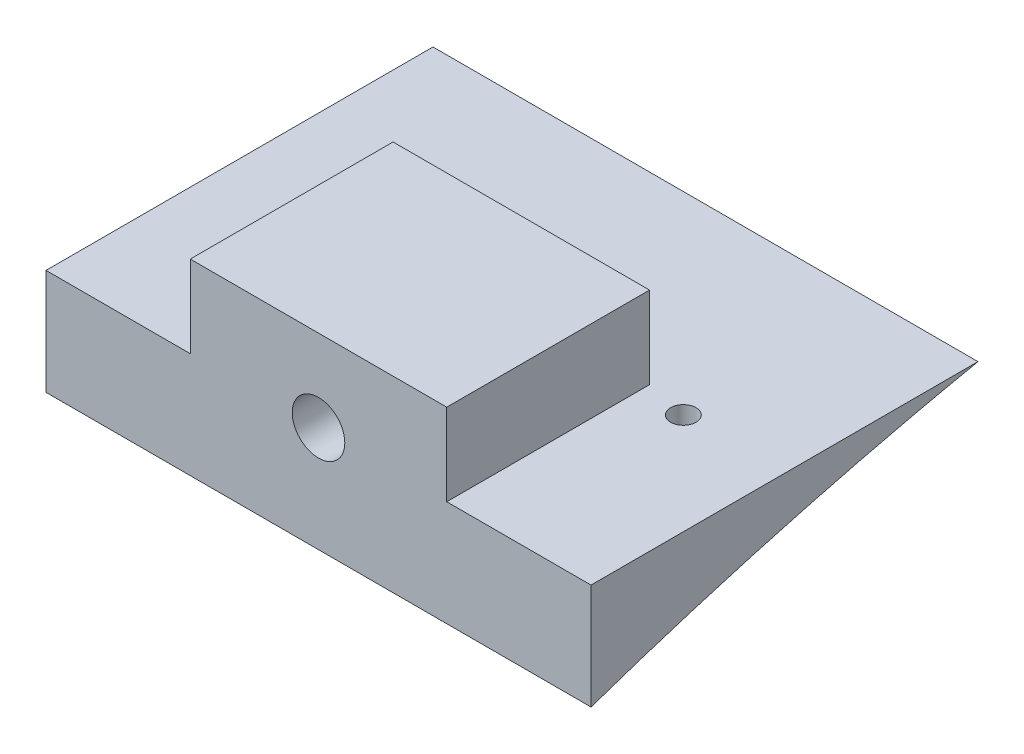
SolidWorks part; units mm, degrees
material "ABS"
ref_plane "Front Plane" through (0, 0, 0) normal (0, 0, 1) x (1, 0, 0)
ref_plane "Top Plane" through (0, 0, 0) normal (0, 1, 0) x (1, 0, 0)
ref_plane "Right Plane" through (0, 0, 0) normal (1, 0, 0) x (0, 0, -1)
curve "Curve1"
  spline degree 3 poles (0, 0.0012, 1.0003) (0, 0.0015, 0.9994) (0, 0.0028, 0.9958) (0, 0.0055, 0.9879) (0, 0.0099, 0.9747) (0, 0.0159, 0.9565) (0, 0.0233, 0.9333) (0, 0.0318, 0.9054) (0, 0.0411, 0.8731) (0, 0.051, 0.8366) (0, 0.0612, 0.7964) (0, 0.0713, 0.7528) (0, 0.0811, 0.7063) (0, 0.0903, 0.6574) (0, 0.0985, 0.6067) (0, 0.1057, 0.5546) (0, 0.1115, 0.5018) (0, 0.1158, 0.4488) (0, 0.1186, 0.3959) (0, 0.1189, 0.3436) (0, 0.1164, 0.2927) (0, 0.1112, 0.2442) (0, 0.1037, 0.1988) (0, 0.0942, 0.157) (0, 0.0831, 0.1194) (0, 0.0711, 0.0865) (0, 0.0584, 0.0585) (0, 0.0457, 0.0357) (0, 0.0334, 0.0184) (0, 0.0218, 0.0064) (0, 0.0108, -0.0005) (0, -0.0003, -0.0011) (0, -0.0092, 0.0055) (0, -0.0148, 0.017) (0, -0.0185, 0.0329) (0, -0.0204, 0.0533) (0, -0.0208, 0.0781) (0, -0.0198, 0.107) (0, -0.0176, 0.1398) (0, -0.0147, 0.176) (0, -0.0111, 0.2153) (0, -0.0074, 0.2574) (0, -0.0037, 0.3019) (0, -0.0005, 0.3484) (0, 0.002, 0.397) (0, 0.0037, 0.4471) (0, 0.0055, 0.4983) (0, 0.0069, 0.5496) (0, 0.0079, 0.6006) (0, 0.0085, 0.6505) (0, 0.0086, 0.699) (0, 0.0083, 0.7455) (0, 0.0076, 0.7894) (0, 0.0065, 0.8302) (0, 0.0053, 0.8675) (0, 0.0039, 0.9007) (0, 0.0027, 0.9296) (0, 0.0013, 0.9539) (0, 0.0006, 0.9727) (0, -0.0011, 0.9872) (0, 0, 0.9944) (0, -0.002, 0.9999) (0, -0.0005, 1) (0, 0, 1) knots 0 0 0 0 0.001372 0.005465 0.012235 0.021602 0.033461 0.047671 0.064081 0.082496 0.102719 0.124527 0.147676 0.171913 0.196978 0.222597 0.248497 0.274385 0.300041 0.32569 0.350525 0.37428 0.396711 0.417577 0.436654 0.453744 0.46868 0.481329 0.491631 0.499616 0.505546 0.510185 0.514824 0.520702 0.528516 0.538466 0.550543 0.564643 0.580638 0.598345 0.617584 0.638174 0.659922 0.682632 0.706121 0.730727 0.7557 0.780732 0.805564 0.829932 0.85357 0.876213 0.89761 0.917519 0.935698 0.951943 0.966047 0.97784 0.987174 0.993932 0.998018 0.999386 1 1 1 1
sketch "Sketch1" plane through (0, 0, 0) normal (1, 0, 0) x (0, 0, -1)
  line L3 (195.725, 0) -> (-195.725, 0) construction
  line L4 (-258.7498, 26.4626) -> (-355.6872, 26.4626)
  line L5 (-355.6872, 26.4626) -> (-355.6872, 0)
  spline S1 degree 3 poles (-355.6872, 0) (-355.3706, 0.108) (-354.109, 0.5382) (-351.285, 1.5029) (-346.6023, 3.0589) (-336.8154, 6.2519) (-320.4299, 11.2778) (-301.3571, 16.5496) (-283.1673, 21.0862) (-270.1079, 24.0716) (-261.8289, 25.8283) (-258.7498, 26.4626) knots 0 0 0 0 0.001372 0.005465 0.012235 0.021602 0.047671 0.082496 0.102719 0.124527 0.137416 0.137416 0.137416 0.137416
  dimension "D1" = 26.4626
  dimension "D2" = 355.6872
  dimension "D3" = 96.9374
extrude "Boss-Extrude1" add sketch "Sketch1" along normal mid plane 136.525
sketch "Sketch2" plane through (0, 26.4626, 0) normal (0, 1, 0) x (1, 0, 0)
  line L0 (-68.2625, -307.2185) -> (68.2625, -307.2185) construction
  line L1 (-68.2625, -258.7498) -> (-68.2625, -355.6872) construction
  line L2 (68.2625, -258.7498) -> (68.2625, -355.6872) construction
  line L3 (-42.926, -307.2185) -> (-42.926, -258.7498) construction
  line L4 (68.2625, -258.7498) -> (-68.2625, -258.7498) construction
  line L5 (42.926, -307.2185) -> (42.926, -258.7498) construction
  line L6 (-68.2625, -286.8403) -> (-42.926, -286.8403) construction
  line L7 (-42.926, -286.8403) -> (42.926, -286.8403) construction
  line L8 (42.926, -286.8403) -> (68.2625, -286.8403) construction
  circle A0 centre (-42.926, -307.2185) radius 3.175
  circle A1 centre (42.926, -307.2185) radius 3.175
  dimension "D1" = 6.35
  dimension "D2" = 6.35
  dimension "D3" = 85.852
extrude "Cut-Extrude1" cut sketch "Sketch2" against normal through all
sketch "Sketch4" plane through (0, 0, 355.6872) normal (0, 0, 1) x (1, 0, 0)
  line L0 (68.2625, 26.4626) -> (-68.2625, 26.4626) construction
  line L1 (-32.1232, 46.9893) -> (32.1232, 46.9893)
  line L2 (-32.1232, 46.9893) -> (-32.1232, 26.4626)
  line L3 (-32.1232, 26.4626) -> (32.1232, 26.4626)
  line L4 (32.1232, 46.9893) -> (32.1232, 26.4626)
  point P6 (0, 26.4626)
extrude "Boss-Extrude2" add sketch "Sketch4" against normal blind 50.8
sketch "Sketch5" plane through (0, 0, 355.6872) normal (0, 0, 1) x (1, 0, 0)
  circle A0 centre (0, 26.4626) radius 6.5828
extrude "Cut-Extrude2" cut sketch "Sketch5" against normal blind 12.7
